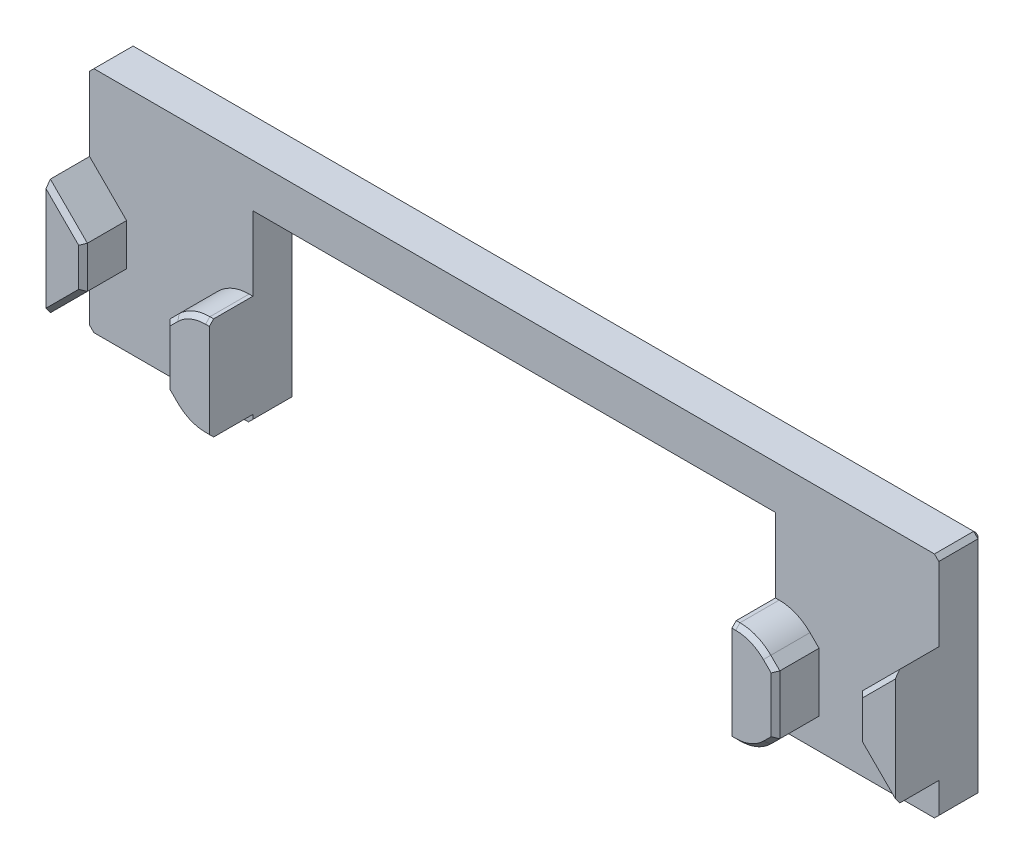
SolidWorks part; units mm, degrees
ref_plane "Front" through (0, 0, 0) normal (0, 0, 1) x (1, 0, 0)
ref_plane "Top" through (0, 0, 0) normal (0, 1, 0) x (1, 0, 0)
ref_plane "Right" through (0, 0, 0) normal (1, 0, 0) x (0, 0, -1)
sketch "Sketch1" plane through (0, 0, 0) normal (0, 0, 1) x (1, 0, 0)
  line L0 (-19.3, 5.25) -> (19.3, 5.25)
  line L5 (19.5, 5.05) -> (19.5, -5.05)
  line L6 (19.3, -5.25) -> (12.2, -5.25)
  line L7 (12, -5.05) -> (12, 3.25)
  line L8 (12, 3.25) -> (-12, 3.25)
  line L9 (-12, 3.25) -> (-12, -5.05)
  line L10 (-12.2, -5.25) -> (-19.3, -5.25)
  line L11 (-19.5, -5.05) -> (-19.5, 5.05)
  line L12 (19.5, 5.05) -> (19.5, 1.8) construction
  line L13 (19.3, -5.25) -> (12, -5.25) construction
  line L14 (19.3, 5.25) -> (-19.3, 5.25) construction
  line L15 (19.5, -5.05) -> (19.3, -5.25)
  line L16 (-12, -5.25) -> (-19.3, -5.25) construction
  line L17 (-19.5, 5.05) -> (-19.5, 1.8) construction
  line L18 (12.2, -5.25) -> (12, -5.05)
  line L19 (19.3, 5.25) -> (19.5, 5.05)
  line L20 (-19.5, 5.05) -> (-19.3, 5.25)
  line L21 (-19.3, -5.25) -> (-19.5, -5.05)
  line L22 (-12, -5.05) -> (-12.2, -5.25)
  point P0 (-19.5, 5.25)
  point P1 (19.5, 5.25)
  point P2 (19.5, -5.25)
  point P4 (12, -5.25)
  point P6 (-19.5, -5.25)
  point P13 (-12, -5.25)
extrude "Boss-Extrude1" add sketch "Sketch1" against normal blind 2
sketch "Sketch3" plane through (0, 0, 0) normal (0, 0, 1) x (1, 0, 0)
  line L3 (12, -5.05) -> (12, 3.25) construction
  line L4 (12, -4.85) -> (12, -0.15)
  line L20 (14, -3.85) -> (14, -1.15)
  line L21 (14, -3.85) -> (14, -1.15)
  line L22 (14, -1.15) -> (13.5858, -0.7358)
  line L23 (14, -1.15) -> (13.5858, -0.7358)
  line L24 (12.1716, -0.15) -> (11.3284, -0.15)
  line L25 (12.1716, -0.15) -> (12, -0.15)
  line L26 (9.9142, -0.7358) -> (9.5, -1.15)
  line L28 (9.5, -1.15) -> (9.5, -3.85)
  line L30 (9.5, -3.85) -> (9.9142, -4.2642)
  line L32 (11.3284, -4.85) -> (12.1716, -4.85)
  line L33 (12, -4.85) -> (12.1716, -4.85)
  line L34 (13.5858, -4.2642) -> (14, -3.85)
  line L35 (13.5858, -4.2642) -> (14, -3.85)
  arc A18 (13.5858, -0.7358) -> (12.1716, -0.15) centre (12.1716, -2.15) ccw
  arc A19 (13.5858, -0.7358) -> (12.1716, -0.15) centre (12.1716, -2.15) ccw
  arc A20 (11.3284, -0.15) -> (9.9142, -0.7358) centre (11.3284, -2.15) ccw
  arc A22 (9.9142, -4.2642) -> (11.3284, -4.85) centre (11.3284, -2.85) ccw
  arc A24 (12.1716, -4.85) -> (13.5858, -4.2642) centre (12.1716, -2.85) ccw
  arc A25 (12.1716, -4.85) -> (13.5858, -4.2642) centre (12.1716, -2.85) ccw
  line M20 (12, 3.25) -> (12, -5.05)
  dimension "D1" = 0
extrude "Boss-Extrude3" add sketch "Sketch3" along normal blind 2 contours L4 | L33 A25 L35 L21 L23 A19 L25 M20 region at (12.92, -2.5, 0)
mirror "Mirror3" about plane through (0, 0, 0) normal (1, 0, 0) of "Boss-Extrude3"
sketch "Sketch4" plane through (0, 0, 0) normal (0, 0, 1) x (1, 0, 0)
  line L4 (19.4, 1.5586) -> (19.5, 1.6586)
  line L5 (19.5, 1.8) -> (19.5, -3.8) construction
  line L6 (19.5, 1.6586) -> (19.5, -3.6586)
  line L7 (19.5, -3.6586) -> (19.4, -3.5586)
  line L8 (19.4, -3.5586) -> (19.4, 1.5586)
  line L9 (19.4, 1.5586) -> (17.8, -0.0414)
  line L10 (17.8, -0.0414) -> (17.8, -1.9586)
  line L11 (17.8, -1.9586) -> (19.4, -3.5586)
  line L12 (19.4, -3.5586) -> (19.4, 1.5586) construction
  line L13 (19.4, 1.5586) -> (17.8, -0.0414)
  line L14 (17.8, -0.0414) -> (17.8, -1.9586)
  line L15 (17.8, -1.9586) -> (19.4, -3.5586)
  dimension "D1" = 0.1
extrude "Aligner" add sketch "Sketch4" along normal blind 2
mirror "Aligners" about plane through (0, 0, 0) normal (1, 0, 0) of "Aligner"
chamfer "Deburs" distance 0.2 angle 45 34 edges at (12, -0.9, -2) (12.1, -5.15, -2) (15.75, -5.25, -2) (19.4, -5.15, -2) (19.5, 0, -2) (19.4, 5.15, -2) (0, 5.25, -2) (-19.4, 5.15, -2) (-19.5, 0, -2) (-19.4, -5.15, -2) (-15.75, -5.25, -2) (-12.1, -5.15, -2) (-12, -0.9, -2) (0, 3.25, -2) (-18.65, 0.8086, 2) (-18.65, -2.8086, 2) (-17.8, -1, 2) (-12.0858, -4.85, 2) (-12.0858, -0.15, 2) (-12.9369, -4.6978, 2) (-12.9369, -0.3022, 2) (-13.7929, -4.0571, 2) (-14, -2.5, 2) (-13.7929, -0.9429, 2) (18.65, -2.8086, 2) (17.8, -1, 2) (18.65, 0.8086, 2) (12.0858, -4.85, 2) (13.7929, -4.0571, 2) (12.9369, -4.6978, 2) (12.0858, -0.15, 2) (12.9369, -0.3022, 2) (14, -2.5, 2) (13.7929, -0.9429, 2)
